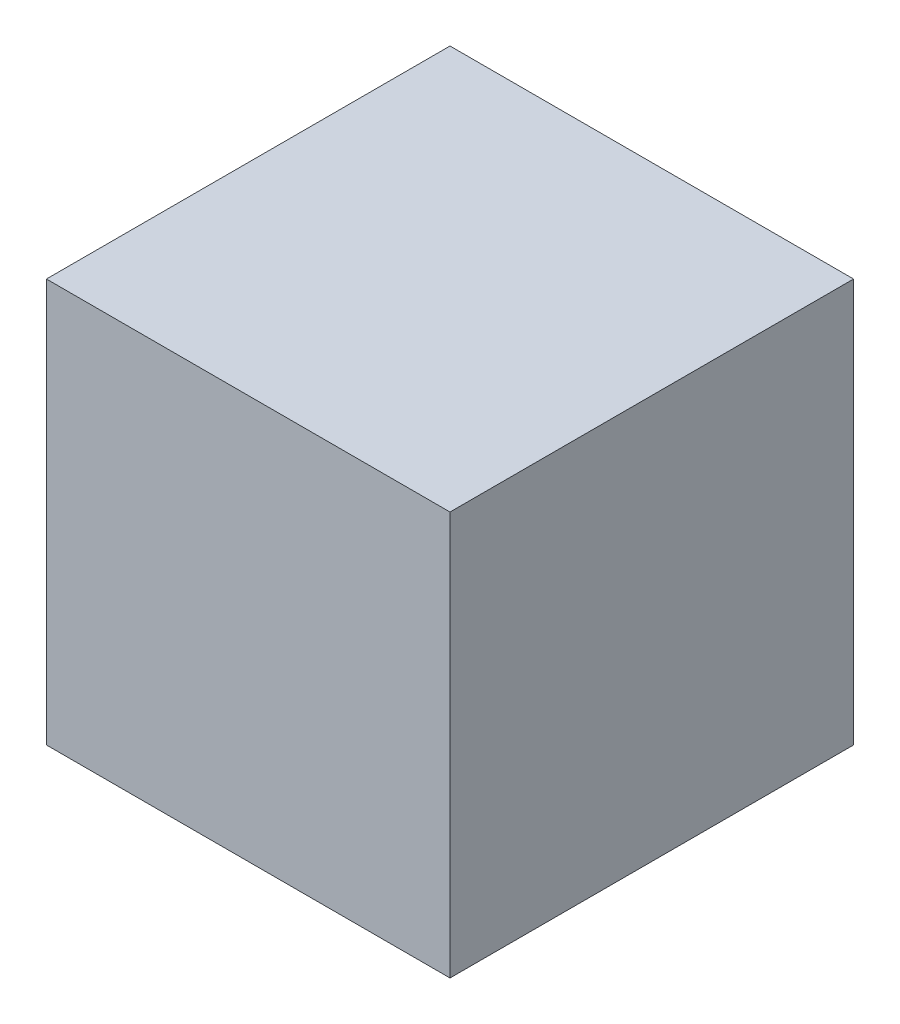
SolidWorks part; units mm, degrees
ref_plane "Alzado" through (0, 0, 0) normal (0, 0, 1) x (1, 0, 0)
ref_plane "Planta" through (0, 0, 0) normal (0, 1, 0) x (1, 0, 0)
ref_plane "Vista lateral" through (0, 0, 0) normal (1, 0, 0) x (0, 0, -1)
sketch "Croquis3" plane through (0, 0, 0) normal (0, 1, 0) x (1, 0, 0)
  line L1 (-50, -50) -> (50, -50)
  line L2 (-50, -50) -> (-50, 50)
  line L3 (-50, 50) -> (50, 50)
  line L4 (50, -50) -> (50, 50)
  line L5 (-50, -50) -> (50, 50) construction
  line L6 (-50, 50) -> (50, -50) construction
  point P0 (0, 0)
  dimension "D1" = 100
  dimension "D2" = 100
extrude "Saliente-Extruir1" add sketch "Croquis3" along normal blind 100
